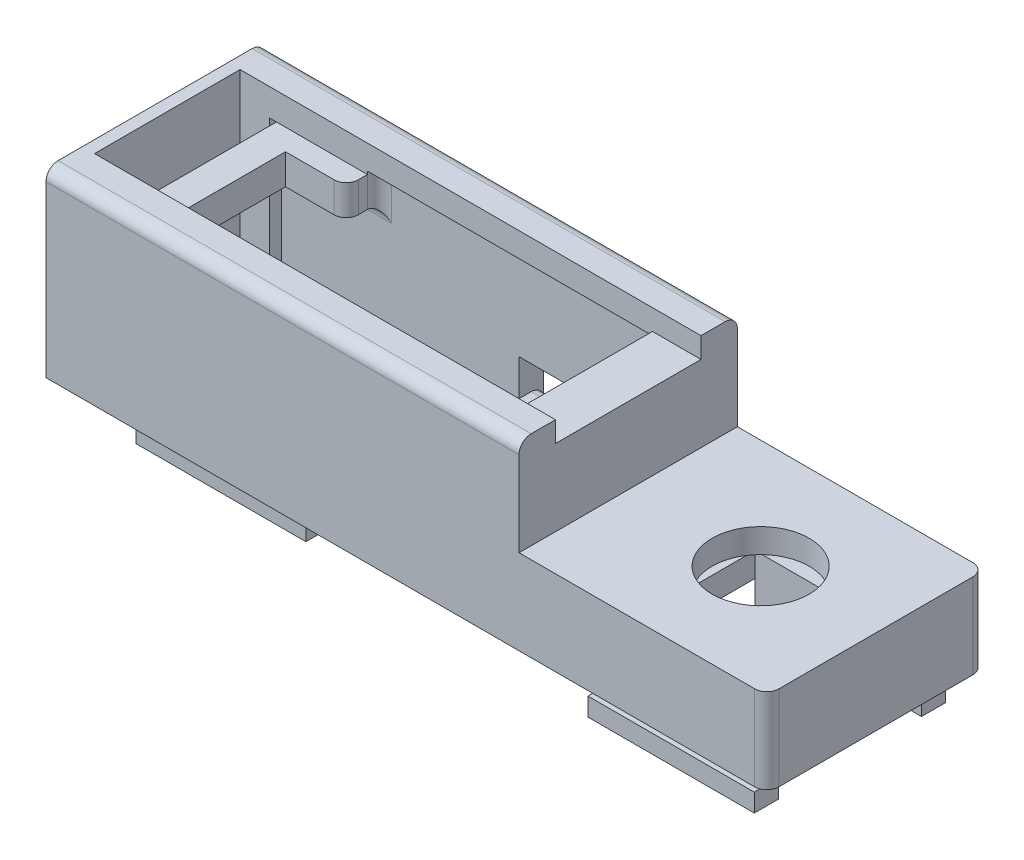
SolidWorks part; units mm, degrees
ref_plane "Front Plane" through (0, 0, 0) normal (0, 0, 1) x (1, 0, 0)
ref_plane "Top Plane" through (0, 0, 0) normal (0, 1, 0) x (1, 0, 0)
ref_plane "Right Plane" through (0, 0, 0) normal (1, 0, 0) x (0, 0, -1)
sketch "Sketch1" plane through (0, 0, 0) normal (0, 1, 0) x (1, 0, 0)
  line L1 (-28, 9) -> (28, 9)
  line L2 (-28, 9) -> (-28, -9)
  line L3 (-28, -9) -> (28, -9)
  line L4 (28, 9) -> (28, -9)
  line L5 (-28, 9) -> (28, -9) construction
  line L6 (-28, -9) -> (28, 9) construction
  point P0 (0, 0)
extrude "Boss-Extrude1" add sketch "Sketch1" along normal blind 2
sketch "Sketch2" plane through (0, 0, 0) normal (0, -1, 0) x (1, 0, 0)
  line L0 (-26, 0) -> (-24.0024, 0) construction
  line L1 (-26, 7) -> (26, 7)
  line L2 (-26, 7) -> (-26, -7)
  line L3 (-26, -7) -> (26, -7)
  line L4 (26, 7) -> (26, -7)
  line L5 (-26, 7) -> (26, -7) construction
  line L6 (-26, -7) -> (26, 7) construction
  line L7 (-24.0024, -4) -> (-24.0024, 4) construction
  line L8 (26, 0) -> (24, 0) construction
  line L9 (-26, 4) -> (-24.0024, 4)
  line L10 (-26, 4) -> (-26, -4)
  line L11 (-26, -4) -> (-24.0024, -4)
  line L12 (-24.0024, 4) -> (-24.0024, -4)
  line L13 (24, 3) -> (24, -3) construction
  line L14 (24, -3) -> (26, -3)
  line L15 (24, -3) -> (24, -5)
  line L16 (24, -5) -> (26, -5)
  line L17 (26, -5) -> (26, -3)
  line L18 (24, 3) -> (26, 3)
  line L19 (24, 3) -> (24, 5)
  line L20 (24, 5) -> (26, 5)
  point P0 (0, 0)
extrude "Boss-Extrude2" add sketch "Sketch2" along normal blind 3 contours L12 L9 L2 L11 | L20 L19 L18 L4 | L15 L16 L4 L14 region at (-25.0012, 0, 0) region at (25, 0, 4) region at (25, 0, -4)
sketch "Sketch3" plane through (-26, 0, 0) normal (-1, 0, 0) x (0, 0, 1)
  line L0 (4, -3) -> (4, 0) construction
  line L1 (-4, -3) -> (4, -3)
  line L2 (-4, -3) -> (-4, -1.5)
  line L3 (-4, -1.5) -> (4, -1.5)
  line L4 (4, -3) -> (4, -1.5)
extrude "Boss-Extrude3" add sketch "Sketch3" along normal blind 2
sketch "Sketch7" plane through (0, 2, 0) normal (0, 1, 0) x (1, 0, 0)
  line L0 (12, 7) -> (26, 7)
  line L1 (-26, 7) -> (-12, 7)
  line L2 (-26, 7) -> (-26, -7)
  line L3 (-26, -7) -> (-12, -7)
  line L4 (26, 7) -> (26, -7)
  line L5 (12, -7) -> (26, -7)
  line L6 (-7.0045, -7) -> (7.0045, -7)
  line L8 (-12, 7) -> (-12, -7)
  line L9 (12, -7) -> (12, 7)
  line L10 (-7.0045, 7) -> (7.0045, 7)
  line L11 (-7.0045, 7) -> (7.0045, 7)
  line L12 (-7.0045, 7) -> (-7.0045, -7)
  line L13 (-7.0045, -7) -> (7.0045, -7)
  line L14 (7.0045, 7) -> (7.0045, -7)
  line L25 (12.142, 5.8928) -> (25.858, 5.8928)
  line L26 (12.142, 5.8928) -> (12.142, -5.8928)
  line L27 (12.142, -5.8928) -> (25.858, -5.8928)
  line L28 (25.858, 5.8928) -> (25.858, -5.8928)
  point P0 (0, 0)
  point P14 (0, 0)
  point P20 (19, 0)
  point P21 (19, 0)
extrude "Boss-Extrude5" add sketch "Sketch7" against normal blind 5 contours L8 L1 L2 L3 | L14 L10 L12 L6 region at (-19, 2, 0) region at (0, 2, 0)
sketch "Sketch8" plane through (0, 0, 9) normal (0, 0, 1) x (1, 0, 0)
  line L0 (-28, 0) -> (28, 0) construction
  line L1 (-7.9878, 0) -> (26.5796, 0)
  line L2 (-7.9878, 0) -> (-7.9878, -3.5717)
  line L3 (-7.9878, -3.5717) -> (26.5796, -3.5717)
  line L4 (26.5796, 0) -> (26.5796, -3.5717)
extrude "Cut-Extrude3" cut sketch "Sketch8" against normal blind 18
extrude "Cut-Extrude4" cut sketch "Sketch7<6>" against normal blind 2 contours L28 L25 L26 L27 region at (19, 2, 0)
sketch "Sketch7<6>" plane through (0, 2, 0) normal (0, 1, 0) x (1, 0, 0) same geometry as "Sketch7"
sketch "Sketch10" plane through (0, 2, 0) normal (0, 1, 0) x (1, 0, 0)
  line L0 (12.142, -5.8928) -> (25.858, -5.8928) construction
  line L1 (12.142, 5.8928) -> (25.858, 5.8928) construction
  line L2 (12.142, -5.8928) -> (25.858, -5.8928)
  line L3 (12.142, 5.8928) -> (25.858, 5.8928)
  line L4 (12.142, 0) -> (25.858, 0) construction
  line L5 (12.142, 5.8928) -> (25.858, 5.8928)
  line L6 (12.142, 5.8928) -> (12.142, 6.8928)
  line L7 (12.142, 6.8928) -> (25.858, 6.8928)
  line L8 (25.858, 5.8928) -> (25.858, 6.8928)
  line L9 (12.142, 5.8928) -> (12.142, -5.8928) construction
  line L10 (25.858, 5.8928) -> (25.858, -5.8928) construction
  line L11 (25.858, -5.8928) -> (25.858, -6.8928)
  line L12 (12.142, -6.8928) -> (25.858, -6.8928)
  line L13 (12.142, -5.8928) -> (12.142, -6.8928)
  line L14 (12.142, -5.8928) -> (25.858, -5.8928)
  line L15 (12.142, -5.8928) -> (25.858, -5.8928)
  line M8 (12.142, 5.8928) -> (25.858, 5.8928)
  line M10 (25.858, -5.8928) -> (12.142, -5.8928)
extrude "Boss-Extrude6" add sketch "Sketch10" against normal blind 5 contours L13 L12 L11 M10 | L8 L7 L6 M8 region at (19, 2, 6.3928) region at (19, 2, -6.3928)
sketch "Sketch11" plane through (0, 0, 6.8928) normal (0, 0, 1) x (1, 0, 0)
  line L0 (12.142, -3) -> (25.858, -3) construction
  line L1 (12.142, -3) -> (25.858, -3)
  line L2 (12.142, -3) -> (12.142, -1.5)
  line L3 (12.142, -1.5) -> (25.858, -1.5)
  line L4 (25.858, -3) -> (25.858, -1.5)
  line L5 (12.142, -3) -> (12.142, 0) construction
  line L6 (25.858, -3) -> (25.858, 0) construction
extrude "Boss-Extrude7" add sketch "Sketch11" along normal blind 1
extrude "Cut-Extrude5" cut sketch "Sketch7<8>" against normal blind 2 contours L14 L10 L12 L6 region at (0, 2, 0)
sketch "Sketch7<8>" plane through (0, 2, 0) normal (0, 1, 0) x (1, 0, 0) same geometry as "Sketch7"
sketch "Sketch12" plane through (0, 0, -6.8928) normal (0, 0, -1) x (-1, 0, 0)
  line L0 (-12.142, -3) -> (-12.142, 0) construction
  line L1 (-25.858, -3) -> (-12.142, -3)
  line L2 (-25.858, -3) -> (-25.858, -1.5)
  line L3 (-25.858, -1.5) -> (-12.142, -1.5)
  line L4 (-12.142, -3) -> (-12.142, -1.5)
extrude "Boss-Extrude8" add sketch "Sketch12" along normal blind 1
sketch "Sketch13" plane through (0, 2, 0) normal (0, 1, 0) x (1, 0, 0)
  line L6 (-7.0045, 7) -> (7.0045, 7) construction
  line L7 (-7.0045, 7) -> (7.0045, 7)
  line L8 (28, -9) -> (28, 9) construction
  line L9 (-28, 9) -> (28, 9)
  line L10 (-28, 9) -> (-28, 7)
  line L11 (-28, 7) -> (28, 7)
  line L12 (28, 9) -> (28, 7)
  line L13 (25.858, 5.8928) -> (25.858, -5.8928) construction
  line L14 (25.858, 5.8928) -> (25.858, -5.8928)
  line L15 (-28, -9) -> (28, -9) construction
  line L16 (25.858, 7) -> (28, 7)
  line L17 (25.858, 7) -> (25.858, -9)
  line L18 (25.858, -9) -> (28, -9)
  line L19 (28, 7) -> (28, -9)
  line L20 (-7.0045, -7) -> (7.0045, -7) construction
  line L21 (-7.0045, -7) -> (7.0045, -7)
  line L22 (-28, 9) -> (-28, -9) construction
  line L23 (-28, -7) -> (25.858, -7)
  line L24 (-28, -7) -> (-28, -9)
  line L25 (-28, -9) -> (25.858, -9)
  line L26 (25.858, -7) -> (25.858, -9)
  line M3 (25.858, 5.8928) -> (25.858, -5.8928)
  line M5 (28, -9) -> (28, 9)
  line M6 (28, 9) -> (-28, 9)
  line M7 (-28, 9) -> (-28, -9)
  line M8 (-28, -9) -> (28, -9)
  line M9 (-7.0045, 7) -> (7.0045, 7)
  line M11 (7.0045, -7) -> (-7.0045, -7)
extrude "Boss-Extrude10" add sketch "Sketch13" along normal blind 5 contours L11 M7 M9 M5 M6 | L11 L17 M3 M8 M5 | L23 L17 M7 M8 M11 region at (0, 2, -8) region at (26.929, 2, 1) region at (-1.071, 2, 8)
sketch "Sketch15" plane through (0, 7, 0) normal (0, 1, 0) x (1, 0, 0)
  line L0 (7.0045, 0) -> (12.142, 0) construction
  line L1 (7.0045, 7) -> (7.0045, -7) construction
  line L2 (12.142, 5.8928) -> (12.142, -5.8928) construction
  line L3 (9.5733, 0) -> (9.5733, 7) construction
  line L4 (-28, 7) -> (25.858, 7) construction
  line L6 (9.5733, 7) -> (25.858, 7)
  line L7 (9.5733, 7) -> (9.5733, -7)
  line L8 (9.5733, -7) -> (25.858, -7)
  line L9 (25.858, 7) -> (25.858, -7)
extrude "Boss-Extrude11" add sketch "Sketch15" against normal blind 2
sketch "Sketch19" plane through (9.5733, 0, 0) normal (-1, 0, 0) x (0, 0, 1)
  line L0 (-7, 5) -> (-7, 7) construction
  line L1 (-7, 5) -> (-7, 7)
  line L2 (7, 5) -> (7, 7) construction
  line L3 (7, 5) -> (7, 7)
  line L4 (-7, 7) -> (7, 7) construction
  line L5 (-7, 7) -> (7, 7)
  line L6 (7, 5) -> (-7, 5) construction
  line L7 (7, 5) -> (-7, 5)
extrude "Boss-Extrude12" add sketch "Sketch19" along normal blind 3
sketch "Sketch20" plane through (0, 7, 0) normal (0, 1, 0) x (1, 0, 0)
  line L1 (-28, -9) -> (2.5733, -9)
  line L2 (-28, -9) -> (-28, -7)
  line L5 (-28, 9) -> (2.5733, 9)
  line L6 (-28, 9) -> (-28, 7)
  line L15 (28, 9) -> (-28, 9) construction
  line L16 (-28, -9) -> (28, -9) construction
  line L17 (6.0868, -9) -> (2.5733, -9)
  line L18 (6.0868, 9) -> (2.5733, 9)
  line L19 (-28, 7) -> (6.5733, 7)
  line L23 (6.5733, 7) -> (6.5733, -7)
  line L24 (6.5733, -7) -> (-28, -7)
  line L25 (6.5733, 1.4626) -> (7.5733, 1.4626) construction
  line L26 (6.0868, 9) -> (7.5733, 9)
  line L27 (7.5733, 9) -> (7.5733, -9)
  line L28 (7.5733, -9) -> (6.0868, -9)
extrude "Boss-Extrude15" add sketch "Sketch20" along normal blind 8
sketch "Sketch24" plane through (6.5733, 0, 0) normal (-1, 0, 0) x (0, 0, 1)
  line L0 (0, 15) -> (0, 13) construction
  line L1 (-7, 15) -> (-6, 15)
  line L2 (-7, 15) -> (-7, 13)
  line L3 (-7, 13) -> (-6, 13)
  line L4 (-6, 15) -> (-6, 13)
  line L5 (-7, 15) -> (7, 15) construction
  line L6 (6, 15) -> (6, 13)
  line L7 (7, 13) -> (6, 13)
  line L8 (7, 15) -> (7, 13)
  line L9 (7, 15) -> (6, 15)
extrude "Boss-Extrude16" add sketch "Sketch24" along normal up to surface (34.5733 mm away) up to face at (-28, 8, 0)
sketch "Sketch26" plane through (6.5733, 0, 0) normal (-1, 0, 0) x (0, 0, 1)
  line L0 (0, 15) -> (0, 13.8) construction
  line L1 (-6, 15) -> (6, 15) construction
  line L2 (-6, 13) -> (-6, 15) construction
  line L3 (-6, 13.8) -> (6, 13.8)
  line L6 (6, 13.8) -> (6, 13)
  line L7 (-6, 13.8) -> (-6, 11.8)
  line L8 (-6, 11.8) -> (6, 11.8)
  line L9 (6, 11.8) -> (6, 13)
extrude "Boss-Extrude17" add sketch "Sketch26" along normal blind 3
sketch "Sketch27" plane through (0, 15, 0) normal (0, 1, 0) x (1, 0, 0)
  line L0 (7.5733, 0) -> (-30.4267, 0) construction
  line L1 (7.5733, -9) -> (7.5733, 9) construction
sketch "Sketch28" plane through (0, 2, 0) normal (0, 1, 0) x (1, 0, 0)
  line L0 (-28, 9) -> (-28, 6) construction
  line L1 (-28, 9) -> (-28, 6)
  line L2 (-28, -6) -> (-28, -9) construction
  line L3 (-28, -6) -> (-28, -9)
  line L4 (-28, -6) -> (-28, 6)
  line L5 (-30.4267, 0) -> (-31.4267, 0) construction
  line L6 (-28, 9) -> (-31.4267, 9)
  line L7 (-31.4267, 9) -> (-31.4267, -9)
  line L8 (-31.4267, -9) -> (-28, -9)
  line L9 (-28, -6) -> (-30.4267, -6)
  line L10 (-30.4267, -6) -> (-30.4267, 6)
  line L11 (-30.4267, 6) -> (-28, 6)
  line M2 (-28, 7) -> (-28, -7)
extrude "Boss-Extrude18" add sketch "Sketch28" against normal up to surface (2 mm away) contours L11 L10 L9 M2 | L5 L10 L11 L1 L6 L7 M2 | L10 L5 L7 L8 L3 L9 M2 region at (-28.0963, 2, -8) region at (-29.2134, 2, 0) region at (-30.9267, 2, 0.0963) up to face at (19, 0, 0)
extrude "Boss-Extrude19" add sketch "Sketch28<3>" along normal up to surface (13 mm away) contours L5 L10 L11 L1 L6 L7 M2 | L10 L5 L7 L8 L3 L9 M2 region at (-28.0963, 2, -8) region at (-30.9267, 2, 0.0963) up to face at (-10.4634, 15, 0)
sketch "Sketch28<3>" plane through (0, 2, 0) normal (0, 1, 0) x (1, 0, 0) same geometry as "Sketch28"
sketch "Sketch29" plane through (0, 0, -7) normal (0, 0, 1) x (1, 0, 0)
  line L0 (3.5733, 13.8) -> (-33.3859, 13.8) construction
  line L1 (-30.4267, 12.7568) -> (-27.4267, 12.7568) construction
  line L2 (-30.4267, 15) -> (-30.4267, 2) construction
  line L3 (-27.4267, 10.2568) -> (-24.9267, 10.2568)
  line L4 (-27.4267, 12.7568) -> (-24.9267, 12.7568)
  line L5 (-27.4267, 12.7568) -> (-27.4267, 10.2568)
  line L8 (-24.9267, 10.2568) -> (-24.9267, 12.7568)
extrude "Boss-Extrude20" add sketch "Sketch29" along normal up to surface (16 mm away) up to face at (1.3822, 7.3333, 9)
sketch "Sketch30" plane through (-24.9267, 0, 0) normal (1, 0, 0) x (0, 0, -1)
  line L0 (-7, 10.2568) -> (7, 10.2568) construction
  line L1 (7, 12.7568) -> (4.2474, 12.7568)
  line L2 (7, 12.7568) -> (7, 10.2568)
  line L3 (7, 10.2568) -> (4.2474, 10.2568)
  line L4 (4.2474, 12.7568) -> (4.2474, 10.2568)
  line L5 (0, 15) -> (0, 11.4067) construction
  line L6 (-6, 15) -> (6, 15) construction
  line L7 (-4.2474, 12.7568) -> (-4.2474, 10.2568)
  line L8 (-7, 10.2568) -> (-4.2474, 10.2568)
  line L9 (-7, 12.7568) -> (-7, 10.2568)
  line L10 (-7, 12.7568) -> (-4.2474, 12.7568)
extrude "Boss-Extrude21" add sketch "Sketch30" along normal blind 5
sketch "Sketch33" plane through (-28, 0, 0) normal (1, 0, 0) x (0, 0, -1)
  line L0 (0, 15.0544) -> (0, 13) construction
  line L1 (6, 13) -> (7, 13)
  line L2 (6, 13) -> (6, 12.7568)
  line L3 (6, 12.7568) -> (7, 12.7568)
  line L4 (7, 13) -> (7, 12.7568)
  line L5 (-7, 13) -> (-7, 12.7568)
  line L6 (-6, 12.7568) -> (-7, 12.7568)
  line L7 (-6, 13) -> (-6, 12.7568)
  line L8 (-6, 13) -> (-7, 13)
extrude "Boss-Extrude22" add sketch "Sketch33" along normal up to surface (8.0733 mm away) up to face at (-19.9267, 11.5068, -5.6237)
sketch "Sketch34" plane through (0, 0, -7) normal (0, 0, 1) x (1, 0, 0)
  line L0 (6.5733, 2) -> (-8.4267, 2)
  line L3 (-8.4267, 5) -> (6.5733, 5)
  line L4 (6.5733, 2) -> (6.5733, 5)
  line L5 (-28, 2) -> (-7.0045, 2) construction
  line L6 (-8.4267, 5) -> (-8.4267, 2)
extrude "Cut-Extrude7" cut sketch "Sketch34" against normal blind 5
fillet "Fillet6" radius 1 1 edges at (-19.9267, 11.6284, -7)
fillet "Fillet7" radius 1 1 edges at (-19.9267, 11.5068, -4.2474)
fillet "Fillet8" radius 1 1 edges at (-19.9267, 11.6284, 7)
fillet "Fillet9" radius 1 1 edges at (-19.9267, 11.5068, 4.2474)
fillet "Fillet10" radius 1 1 edges at (-27.4267, 11.5068, -7)
fillet "Fillet11" radius 1 1 edges at (-27.4267, 11.5068, 7)
fillet "Fillet12" radius 1 2 edges at (-26, -2.25, 4) (-26, -2.25, -4)
fillet "Fillet13" radius 1 2 edges at (-23.4634, 10.2568, -7) (-23.4634, 10.2568, 7)
fillet "Fillet16" radius 1 2 edges at (-0.9267, 5, -9) (-0.9267, 2, -9)
sketch "Sketch35" plane through (0, 13.8, 0) normal (0, 1, 0) x (1, 0, 0)
  line L1 (3.5733, 6) -> (6.5733, 6)
  line L2 (3.5733, 6) -> (3.5733, -6)
  line L3 (3.5733, -6) -> (6.5733, -6)
  line L4 (6.5733, 6) -> (6.5733, -6)
extrude "Cut-Extrude8" cut sketch "Sketch35" against normal blind 0.5
fillet "Fillet20" radius 1 2 edges at (28, 3.5, -9) (28, 3.5, 9)
sketch "Sketch37" plane through (0, 7, 0) normal (0, 1, 0) x (1, 0, 0)
  circle A2 centre (18.492, 0) radius 4
extrude "Cut-Extrude9" cut sketch "Sketch37" against normal blind 5
sketch "Sketch38" plane through (0, 7, 0) normal (0, 1, 0) x (1, 0, 0)
  line L0 (8.492, 0) -> (8.492, 9) construction
  line L1 (27, 9) -> (7.5733, 9) construction
  line L2 (8.492, 0) -> (8.492, -9) construction
  line L3 (7.5733, -9) -> (27, -9) construction
  circle A0 centre (18.492, 0) radius 10
sketch "Sketch39" plane through (0, 15, 0) normal (0, 1, 0) x (1, 0, 0)
  line L0 (6.5733, 6) -> (7.5733, 6) construction
  line L1 (7.5733, -9) -> (7.5733, 9) construction
  line L3 (7.5733, 6) -> (6.5733, 6)
  line L4 (7.5733, 6) -> (7.5733, -6)
  line L5 (7.5733, -6) -> (6.5733, -6)
  line L6 (6.5733, 6) -> (6.5733, -6)
extrude "Cut-Extrude11" cut sketch "Sketch39" against normal up to surface (1.7 mm away) up to face at (5.0733, 13.3, 0)
fillet "Fillet25" radius 1 5 edges at (-27.7442, 9.8197, 6.8265) (-27.4267, 10.2556, 6.0479) (-27.62, 9.9838, -6.6866) (-27.4267, 10.2556, -6.0479) (-27.4267, 10.2568, 0)
fillet "Fillet28" radius 1 2 edges at (-11.9267, 15, -9) (-11.9267, 15, 9)
